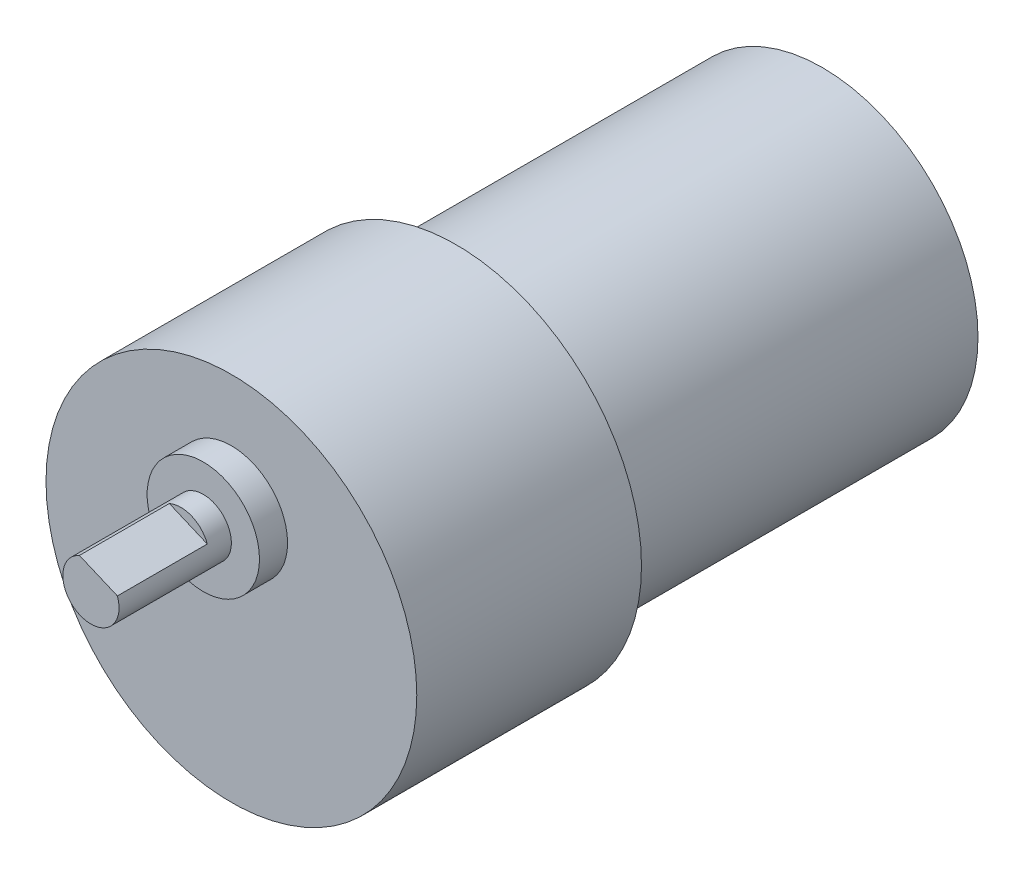
SolidWorks part; units mm, degrees
ref_plane "Front Plane" through (0, 0, 0) normal (0, 0, 1) x (1, 0, 0)
ref_plane "Top Plane" through (0, 0, 0) normal (0, 1, 0) x (1, 0, 0)
ref_plane "Right Plane" through (0, 0, 0) normal (1, 0, 0) x (0, 0, -1)
sketch "Sketch1" plane through (0, 0, 0) normal (0, 0, 1) x (1, 0, 0)
  circle A0 centre (0, 0) radius 16.5
  dimension "D1" = 33
extrude "Boss-Extrude1" add sketch "Sketch1" along normal blind 20
sketch "Sketch2" plane through (0, 0, 0) normal (0, 0, -1) x (-1, 0, 0)
  circle A0 centre (0, 0) radius 13.85
  dimension "D1" = 27.7
extrude "Boss-Extrude2" add sketch "Sketch2" along normal blind 32.6
sketch "Sketch3" plane through (0, 0, -32.6) normal (0, 0, -1) x (-1, 0, 0)
  circle A0 centre (0, 0) radius 5
  dimension "D1" = 10
extrude "Boss-Extrude3" add sketch "Sketch3" along normal blind 2.2
sketch "Sketch4" plane through (0, 0, -34.8) normal (0, 0, -1) x (-1, 0, 0)
  circle A0 centre (0, 0) radius 1.15
  dimension "D1" = 2.3
extrude "Boss-Extrude4" add sketch "Sketch4" along normal blind 3.3
sketch "Sketch5" plane through (0, 0, 20) normal (0, 0, 1) x (1, 0, 0)
  line L0 (0, 16.5) -> (0, -16.5) construction
  line L1 (-16.5, 0) -> (16.5, 0) construction
  circle A0 centre (0, 0) radius 16.5 construction
  circle A1 centre (0, 6) radius 5
  dimension "D2" = 10
  dimension "D1" = 6
extrude "Boss-Extrude5" add sketch "Sketch5" along normal blind 2.5
sketch "Sketch6" plane through (0, 0, 22.5) normal (0, 0, 1) x (1, 0, 0)
  circle A0 centre (0, 6) radius 2.5
  dimension "D1" = 5
extrude "Boss-Extrude6" add sketch "Sketch6" along normal blind 10
sketch "Sketch7" plane through (0, 0, 32.5) normal (0, 0, 1) x (1, 0, 0)
  line L0 (-1.0242, 8.2806) -> (2.3522, 6.8469)
  line L1 (0, 8.5) -> (0, 3.5) construction
  circle A0 centre (0, 6) radius 2.5 construction
  arc A1 (-1.0242, 8.2806) -> (2.3522, 6.8469) centre (0, 6) cw
  dimension "D1" = 4
extrude "Cut-Extrude1" cut sketch "Sketch7" against normal blind 8
equation "\"motor offset\"= 6mm"
equation "\"thickness0.25\"= 0.225in"
equation "\"thickness0.125\"= 0.122in"
